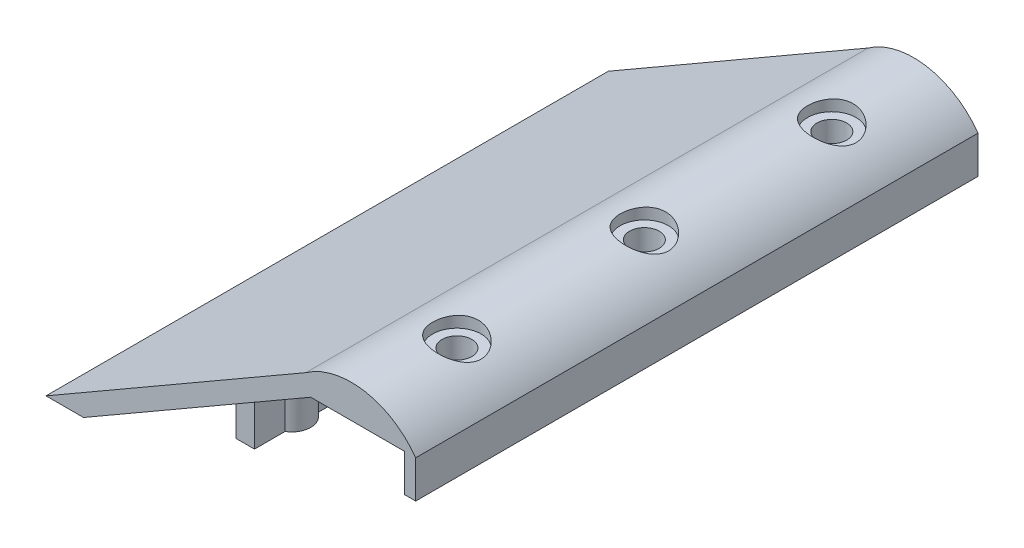
SolidWorks part; units mm, degrees
ref_plane "Alzado" through (0, 0, 0) normal (0, 0, 1) x (1, 0, 0)
ref_plane "Planta" through (0, 0, 0) normal (0, 1, 0) x (1, 0, 0)
ref_plane "Vista lateral" through (0, 0, 0) normal (1, 0, 0) x (0, 0, -1)
sketch "Croquis1" plane through (0, 0, 0) normal (0, 0, 1) x (1, 0, 0)
  line L0 (0, 34.3848) -> (0, -4.3701) construction
  line L1 (-35.1904, 0) -> (25, 0) construction
  line L2 (0, 0) -> (25, 0)
  line L3 (25, 0) -> (25, 5) construction
  line L4 (25, 5) -> (-1.3397, 5) construction
  line L5 (-1.3397, 5) -> (-70.6218, -35)
  line L6 (-70.6218, -35) -> (-60.6218, -35)
  line L7 (-60.6218, -35) -> (0, 0)
  line L8 (-73.772, -35) -> (41.2109, -35) construction
  line L9 (34.3149, -26) -> (-26.4016, -26) construction
  line L10 (-77.6138, -56) -> (49.339, -56) construction
  line L11 (0, 0) -> (25, 0) construction
  line L12 (0, 0) -> (25, 0)
  line L13 (0, 0) -> (25, 0)
  line L14 (25, 0) -> (25, -10)
  line L15 (25, -10) -> (28, -10)
  line L16 (28, -10) -> (28, 0)
  line L17 (-4.6669, 0) -> (44.3879, 0) construction
  arc A0 (-1.3397, 5) -> (28, 0) centre (10.8301, -12.1699) cw
  dimension "D8" = 10
  dimension "D10" = 21.0454
  dimension "D1" = 25
  dimension "D2" = 30
  dimension "D3" = 5
  dimension "D4" = 5
  dimension "D5" = 26
  dimension "D6" = 30
  dimension "D7" = 35
  dimension "D9" = 3
extrude "Saliente-Extruir1" add sketch "Croquis1" along normal mid plane 150 contours A0 L5 L6 L7 L2 L14 L15 L16 region at (-30.8506, -16.5652, 0)
ref_plane "Plano Tangente Para Perforacion" through (0, 8.8756, 0) normal (0, 1, 0) x (1, 0, 0)
ref_plane "Bases Soporte" through (0, -15, 0) normal (0, 1, 0) x (1, 0, 0)
sketch "Croquis2" plane through (0, -15, 0) normal (0, 1, 0) x (1, 0, 0)
  line L0 (122.6306, 0) -> (-182.6306, 0) construction
  line L1 (0, 52.1261) -> (0, -47.2849) construction
  line L2 (-30, 99.6856) -> (-30, -100.7612) construction
  line L3 (-32.5, 4.3301) -> (-32.5, 12.5)
  line L4 (-32.5, -12.5) -> (-27.5, -12.5)
  line L5 (-32.5, -12.5) -> (-32.5, -4.3301)
  line L6 (-32.5, 12.5) -> (-27.5, 12.5)
  line L7 (-27.5, -12.5) -> (-27.5, -4.3301)
  line L8 (-32.5, -12.5) -> (-27.5, 12.5) construction
  line L9 (-32.5, 12.5) -> (-27.5, -12.5) construction
  line L10 (-27.5, 4.3301) -> (-27.5, 12.5)
  line L17 (-32.5, 54.3301) -> (-32.5, 62.5)
  line L24 (-32.5, 37.5) -> (-27.5, 37.5)
  line L25 (-32.5, 37.5) -> (-32.5, 45.6699)
  line L26 (-32.5, 62.5) -> (-27.5, 62.5)
  line L27 (-27.5, 37.5) -> (-27.5, 45.6699)
  line L28 (-27.5, 54.3301) -> (-27.5, 62.5)
  line L29 (-32.5, 37.5) -> (-27.5, 62.5) construction
  line L30 (-32.5, 62.5) -> (-27.5, 37.5) construction
  line L31 (-32.5, 4.3301) -> (-32.5, 54.3301) construction
  line L32 (-32.5, -45.6699) -> (-32.5, -37.5)
  line L33 (-32.5, -62.5) -> (-27.5, -62.5)
  line L34 (-32.5, -62.5) -> (-32.5, -54.3301)
  line L35 (-32.5, -37.5) -> (-27.5, -37.5)
  line L36 (-27.5, -62.5) -> (-27.5, -54.3301)
  line L37 (-27.5, -45.6699) -> (-27.5, -37.5)
  line L38 (-32.5, -62.5) -> (-27.5, -37.5) construction
  line L39 (-32.5, -37.5) -> (-27.5, -62.5) construction
  line L40 (-32.5, 4.3301) -> (-32.5, -45.6699) construction
  arc A0 (-32.5, 4.3301) -> (-32.5, -4.3301) centre (-30, 0) ccw
  arc A2 (-27.5, -4.3301) -> (-27.5, 4.3301) centre (-30, 0) ccw
  arc A6 (-32.5, 54.3301) -> (-32.5, 45.6699) centre (-30, 50) ccw
  arc A7 (-27.5, 45.6699) -> (-27.5, 54.3301) centre (-30, 50) ccw
  arc A8 (-32.5, -45.6699) -> (-32.5, -54.3301) centre (-30, -50) ccw
  arc A9 (-27.5, -54.3301) -> (-27.5, -45.6699) centre (-30, -50) ccw
  dimension "D1" = 10
  dimension "D2" = 30
  dimension "D3" = 5
  dimension "D4" = 25
  dimension "D5" = 2
  dimension "D6" = 50
  dimension "D8" = 50
  dimension "D7" = 2
extrude "Saliente-Extruir2" add sketch "Croquis2" against normal blind 17 and the other way up to surface other way up to face at (-30.3109, -17.5, 0)
sketch "Croquis3" plane through (0, 8.8756, 0) normal (0, 1, 0) x (1, 0, 0)
  line L0 (0, -113.8566) -> (0, 103.3108) construction
  line L1 (55.4509, 0) -> (-87.9325, 0) construction
  line L2 (14, 0) -> (14, 50) construction
  line L3 (14, 0) -> (14, -50) construction
  line L6 (28, 75) -> (-1.3397, 75)
  line L7 (-1.3397, 75) -> (-1.3397, -75)
  line L8 (-1.3397, -75) -> (28, -75)
  line L9 (28, -75) -> (28, 75)
  line L10 (28, 75) -> (-1.3397, 75)
  line L11 (-1.3397, 75) -> (-1.3397, -75)
  line L12 (-1.3397, -75) -> (28, -75)
  line L13 (28, -75) -> (28, 75)
  circle A0 centre (14, 0) radius 3.9687
  circle A1 centre (14, 50) radius 3.9688
  circle A2 centre (14, -50) radius 3.9687
  dimension "D3" = 7.9375
  dimension "D2" = 14
  dimension "D5" = 50
  dimension "D7" = 50
  dimension "D1" = 0
  dimension "D4" = 2
  dimension "D6" = 2
extrude "Cortar-Extruir1" cut sketch "Croquis3" against normal blind 10 contours A2 | A0 | A1 region at (14, 8.8756, 0) region at (14, 8.8756, -50) region at (14, 8.8756, 50)
sketch "Croquis4" plane through (0, 8.8756, 0) normal (0, 1, 0) x (1, 0, 0)
  circle A0 centre (14, 50) radius 3.9688 construction
  circle A1 centre (14, -50) radius 3.9688 construction
  circle A2 centre (14, 0) radius 3.9687 construction
  circle A3 centre (14, 50) radius 3.9688
  circle A4 centre (14, -50) radius 3.9688
  circle A5 centre (14, 0) radius 3.9687
  circle A6 centre (14, 50) radius 6.4688
  circle A7 centre (14, 0) radius 6.4688
  circle A8 centre (14, -50) radius 6.4688
  dimension "D1" = 2.5
extrude "Cortar-Extruir2" cut sketch "Croquis4" against normal blind 3
ref_plane "Mordazas" through (0, -35, 0) normal (0, -1, 0) x (-1, 0, 0)
sketch "Croquis7" plane through (0, -35, 0) normal (0, -1, 0) x (-1, 0, 0)
  line L0 (-54.6749, 0) -> (103.8779, 0) construction
  line L1 (50.6218, -79.2787) -> (50.6218, 99.1128) construction
  line L2 (70.6218, -75) -> (70.6218, 75) construction
  line L3 (50.6218, 0) -> (50.6218, 50) construction
  line L4 (50.6218, 0) -> (50.6218, -50) construction
  circle A0 centre (50.6218, 0) radius 1.9844
  circle A1 centre (50.6218, 50) radius 1.9844
  circle A2 centre (50.6218, -50) radius 1.9844
  dimension "D2" = 3.9688
  dimension "D1" = 20
  dimension "D4" = 50
  dimension "D6" = 50
  dimension "D3" = 2
  dimension "D5" = 2
extrude "Saliente-Extruir3" add sketch "Croquis7" against normal up to surface (5.7735 mm away) up to face at (-30, -17.3205, -50)
sketch "Croquis8" plane through (0, 0, 0) normal (0, 0, 1) x (1, 0, 0)
  line L0 (37.632, 0) -> (-83.7339, 0) construction
  line L1 (-50.6218, 18.5207) -> (-50.6218, -41.8553) construction
  line L2 (-52.6062, -30.3722) -> (-52.6062, -35) construction
  line L3 (-52.6062, -30.3722) -> (-52.6062, -35)
  line L4 (-52.6062, -30.3722) -> (-48.6374, -28.0808) construction
  line L5 (-52.6062, -30.3722) -> (-48.6374, -28.0808)
  line L6 (-48.6374, -35) -> (-48.6374, -28.0808) construction
  line L7 (-48.6374, -35) -> (-48.6374, -28.0808)
  line L8 (-52.6062, -35) -> (-48.6374, -35) construction
  line L9 (-52.6062, -35) -> (-48.6374, -35)
  line L11 (-53.6079, -33.5) -> (-47.5693, -33.5) construction
  arc A0 (-52.6062, -33.5) -> (-48.6374, -33.5) centre (-50.6218, -32.9374) ccw
  point P9 (-50.6218, -35)
  dimension "D1" = 1.5
extrude "Cortar-Extruir3" cut sketch "Croquis8" against normal mid plane 150 contours L9 L3 | L7 L9 region at (-52.1522, -34.6047, 0) region at (-49.0914, -34.6047, 0)
sketch "Croquis9" plane through (0, -32, 0) normal (0, -1, 0) x (1, 0, 0)
  line L0 (42.5355, 0) -> (-78.3445, 0) construction
  line L1 (-30, 66.7523) -> (-30, -66.0993) construction
  line L2 (-30, 0) -> (-30, 50) construction
  line L3 (-30, 0) -> (-30, -50) construction
  line L7 (-27.5, -12.5) -> (-27.5, -4.3301)
  line L8 (-27.5, 4.3301) -> (-27.5, 12.5)
  line L9 (-27.5, 12.5) -> (-32.5, 12.5)
  line L10 (-32.5, 12.5) -> (-32.5, 4.3301)
  line L11 (-32.5, -4.3301) -> (-32.5, -12.5)
  line L12 (-32.5, -12.5) -> (-27.5, -12.5)
  line L13 (-27.5, -12.5) -> (-27.5, -4.3301)
  line L14 (-27.5, 4.3301) -> (-27.5, 12.5)
  line L15 (-27.5, 12.5) -> (-32.5, 12.5)
  line L16 (-32.5, 12.5) -> (-32.5, 4.3301)
  line L17 (-32.5, -4.3301) -> (-32.5, -12.5)
  line L18 (-32.5, -12.5) -> (-27.5, -12.5)
  circle A0 centre (-30, 0) radius 1
  circle A1 centre (-30, 50) radius 1
  arc A2 (-27.5, -4.3301) -> (-27.5, 4.3301) centre (-30, 0) ccw
  arc A3 (-32.5, 4.3301) -> (-32.5, -4.3301) centre (-30, 0) ccw
  arc A4 (-27.5, -4.3301) -> (-27.5, 4.3301) centre (-30, 0) ccw
  arc A5 (-32.5, 4.3301) -> (-32.5, -4.3301) centre (-30, 0) ccw
  circle A6 centre (-30, -50) radius 1
  dimension "D2" = 2
  dimension "D4" = 50
  dimension "D6" = 50
  dimension "D1" = 0
  dimension "D3" = 2
  dimension "D5" = 2
extrude "Cortar-Extruir4" cut sketch "Croquis9" against normal blind 10 contours A0 | A1 | A6 region at (-30, -32, 0) region at (-30, -32, 50)
